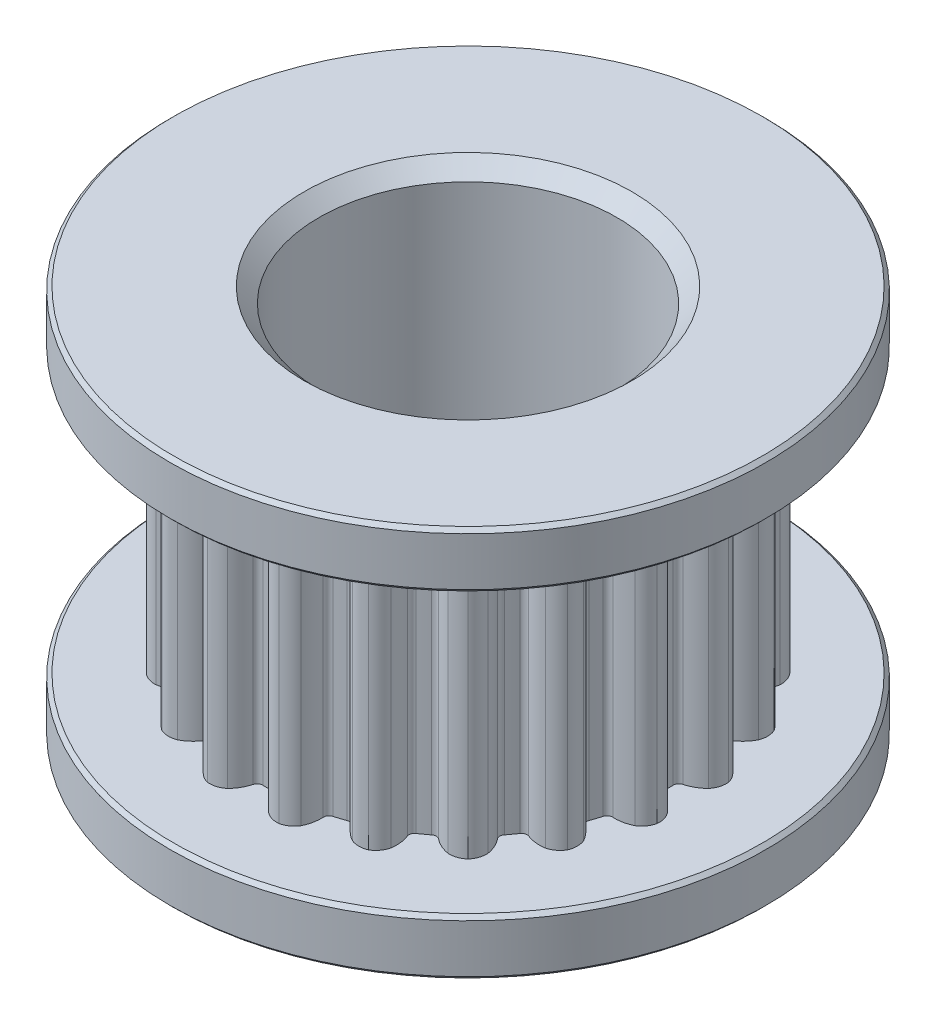
SolidWorks part; units mm, degrees
material "6061 Alloy"
ref_plane "Front Plane" through (0, 0, 0) normal (0, 0, 1) x (1, 0, 0)
ref_plane "Top Plane" through (0, 0, 0) normal (0, 1, 0) x (1, 0, 0)
ref_plane "Right Plane" through (0, 0, 0) normal (1, 0, 0) x (0, 0, -1)
sketch "BodyS" plane through (0, 0, 0) normal (0, 0, 1) x (1, 0, 0)
  line L0 (6.11, -3.75) -> (6.11, 3.75)
  line L1 (6.11, 3.75) -> (8, 3.75)
  line L2 (8, 3.75) -> (8, 5.25)
  line L3 (8, 5.25) -> (4, 5.25)
  line L4 (4, 5.25) -> (4, 2.25)
  line L5 (4, 2.25) -> (3.5, 2.25)
  line L6 (3.5, 2.25) -> (3.5, -2.25)
  line L7 (3.5, -2.25) -> (4, -2.25)
  line L8 (4, -2.25) -> (4, -5.25)
  line L9 (4, -5.25) -> (8, -5.25)
  line L10 (8, -5.25) -> (8, -3.75)
  line L11 (8, -3.75) -> (6.11, -3.75)
  line L12 (0, 0) -> (3.5, 0) construction
  line L13 (0, 5.25) -> (0, -5.25) construction
  dimension "BearingOD" = 8
  dimension "Height" = 10.5
  dimension "FlangeHeight" = 1.5
  dimension "BearingHeight" = 3
  dimension "BearingRestDiaControl" = 0.5
  dimension "RefBodyInnerDiameter" = 7
  dimension "FlangeDiaControl" = 4
  dimension "RefFlangeDia" = 16
  dimension "BeltPathDiaControl" = 2.11
  dimension "RefBeltPathDia" = 12.22
revolve "Body" add sketch "BodyS" angle 360 about L13
sketch "GT2ProfileS" plane through (0, 0, 0) normal (0, 1, 0) x (1, 0, 0)
  line L1 (0, -6.11) -> (0, -5.36) construction
  line L2 (-0.9955, -6.0283) -> (-0.8733, -5.2884) construction
  line L3 (0, 0) -> (-0.8733, -5.2884) construction
  line L4 (0.9955, -6.0283) -> (0, 0) construction
  arc A3 (0.2997, -5.4688) -> (0.1507, -5.3579) centre (0.1549, -5.5078) ccw
  arc A4 (-0.9955, -6.0283) -> (0.9955, -6.0283) centre (0, 0) ccw
  arc A5 (-0.2997, -5.4688) -> (-0.1507, -5.3579) centre (-0.1549, -5.5078) cw
  arc A6 (-0.2997, -5.4688) -> (-0.5497, -5.907) centre (-1.2653, -5.2085) cw
  circle A7 centre (0, 0) radius 6.11 construction
  arc A8 (-0.1507, -5.3579) -> (0.1507, -5.3579) centre (0, 0) ccw
  arc A9 (-0.5497, -5.907) -> (-0.9955, -6.0283) centre (-0.9051, -5.4808) cw
  arc A10 (0.2997, -5.4688) -> (0.5497, -5.907) centre (1.2653, -5.2085) ccw
  arc A11 (0.5497, -5.907) -> (0.9955, -6.0283) centre (0.9051, -5.4808) ccw
  circle A12 centre (0, 0) radius 5.36 construction
  dimension "BottomRadius" = 0.15
  dimension "MidRadius" = 1
  dimension "TopRadius" = 0.555
  dimension "Height" = 0.75
  dimension "XDistMidRadius" = 0.4
  dimension "ArcLengthAngle" = 18.755
  dimension "ArcLength" = 2
sketch "ThruBoreS" plane through (0, 0, 0) normal (0, 1, 0) x (1, 0, 0)
  circle A0 centre (0, 0) radius 4
  circle A2 centre (0, 0) radius 4 construction
extrude "ThruBore" cut sketch "ThruBoreS" against normal through all both and the other way through all
extrude "GT2Profile" cut sketch "GT2ProfileS" against normal up to surface and the other way up to surface up to face at (0, -3.75, 6.11) other way up to face at (0, 3.75, 8)
pattern_circular "GT2 Groove CP" count 20 over 360 about axis through (0, 5.25, 0) along (0, 1, 0) of "GT2Profile"
chamfer "InnerC" distance 0.4 angle 45 2 edges at (0, -5.25, 4) (0, 5.25, 4)
chamfer "OuterC" distance 0.1 angle 45 4 edges at (0, -5.25, 8) (0, -3.75, 8) (0, 3.75, 8) (0, 5.25, 8)
equation "\"NumTeeth@GT2 Groove CP\"=int(360/\"ArcLengthAngle@GT2ProfileS\")+1"
